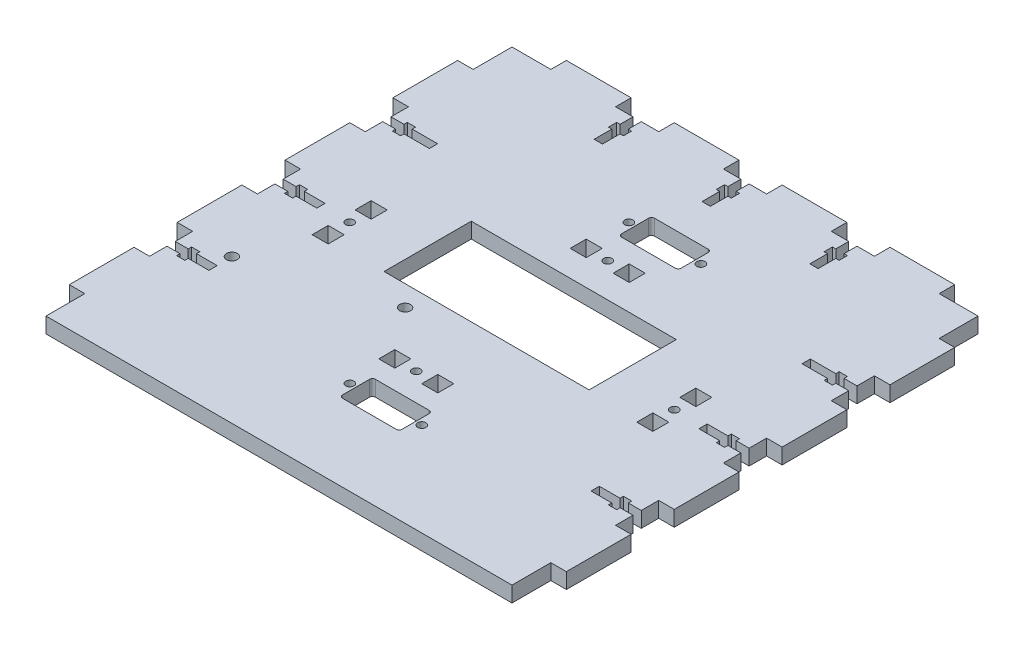
SolidWorks part; units mm, degrees
material "Oak"
ref_plane "Front Plane" through (0, 0, 0) normal (0, 0, 1) x (1, 0, 0)
ref_plane "Top Plane" through (0, 0, 0) normal (0, 1, 0) x (1, 0, 0)
ref_plane "Right Plane" through (0, 0, 0) normal (1, 0, 0) x (0, 0, -1)
sketch "Sketch1" plane through (0, 0, 0) normal (0, 1, 0) x (1, 0, 0)
  line L0 (0, -90) -> (0, 90) construction
  line L2 (90, 43.2667) -> (85, 43.2667)
  line L3 (90, 43.2667) -> (90, 40.0667)
  line L4 (90, 40.0667) -> (85, 40.0667)
  line L5 (72, 43.2667) -> (72, 40.0667)
  line L6 (81.8, 40.0667) -> (72, 40.0667)
  line L7 (81.8, 44.5667) -> (85, 44.5667)
  line L8 (81.8, 44.5667) -> (81.8, 43.2667)
  line L9 (81.8, 38.7667) -> (85, 38.7667)
  line L10 (85, 44.5667) -> (85, 43.2667)
  line L11 (81.8, 40.0667) -> (81.8, 38.7667)
  line L12 (81.8, 43.2667) -> (72, 43.2667)
  line L13 (85, 40.0667) -> (85, 38.7667)
  line L14 (90, 43.2667) -> (90, 50) construction
  line L15 (90, 40.0667) -> (90, 33.3333) construction
  line L16 (-85, 40.0667) -> (-85, 38.7667)
  line L17 (-81.8, 43.2667) -> (-72, 43.2667)
  line L18 (-81.8, 40.0667) -> (-81.8, 38.7667)
  line L19 (-85, 44.5667) -> (-85, 43.2667)
  line L20 (-81.8, 38.7667) -> (-85, 38.7667)
  line L21 (-81.8, 44.5667) -> (-81.8, 43.2667)
  line L22 (-81.8, 44.5667) -> (-85, 44.5667)
  line L23 (-81.8, 40.0667) -> (-72, 40.0667)
  line L24 (-72, 43.2667) -> (-72, 40.0667)
  line L25 (-90, 40.0667) -> (-85, 40.0667)
  line L26 (-90, 43.2667) -> (-90, 40.0667)
  line L27 (-90, 43.2667) -> (-85, 43.2667)
  line L86 (65.8, -11.4) -> (59.6, -11.4)
  line L87 (-65.8, -5.2) -> (-59.6, -5.2)
  line L90 (-65.7, 11.3) -> (-65.7, 5.3) construction
  line L91 (-65.7, 5.3) -> (-59.7, 5.3) construction
  line L92 (-59.7, 5.3) -> (-59.7, 11.3) construction
  line L93 (-59.7, 11.3) -> (-65.7, 11.3) construction
  line L98 (-65.7, 11.3) -> (-65.7, 5.3) construction
  line L99 (-65.7, 5.3) -> (-59.7, 5.3) construction
  line L100 (-59.7, 5.3) -> (-59.7, 11.3) construction
  line L101 (-59.7, 11.3) -> (-65.7, 11.3) construction
  line L102 (-59.6, 11.4) -> (-65.8, 11.4)
  line L103 (-65.8, 11.4) -> (-65.8, 5.2)
  line L104 (-65.8, 5.2) -> (-59.6, 5.2)
  line L105 (-59.6, 5.2) -> (-59.6, 11.4)
  line L114 (65.8, 5.2) -> (59.6, 5.2)
  line L115 (59.6, 5.2) -> (59.6, 11.4)
  line L116 (65.8, 11.4) -> (65.8, 5.2)
  line L117 (59.6, 11.4) -> (65.8, 11.4)
  line L118 (-62.7, 5.2) -> (-62.7, -5.2) construction
  line L119 (-65.8, -5.2) -> (-65.8, -11.4)
  line L120 (-65.8, -11.4) -> (-59.6, -11.4)
  line L121 (-59.6, -5.2) -> (-59.6, -11.4)
  line L122 (59.6, -5.2) -> (59.6, -11.4)
  line L123 (65.8, -5.2) -> (59.6, -5.2)
  line L135 (65.8, -5.2) -> (65.8, -11.4)
  line L142 (-6.1, -59.15) -> (-6.1, -48.65) construction
  line L143 (-5.25, -47.8) -> (15.55, -47.8) construction
  line L144 (15.55, -60) -> (-5.25, -60) construction
  line L145 (16.4, -48.65) -> (16.4, -59.15) construction
  line L146 (-6.1, -59.15) -> (-6.1, -48.65) construction
  line L151 (-5.25, -47.8) -> (15.55, -47.8) construction
  line L152 (15.55, -60) -> (-5.25, -60) construction
  line L153 (16.4, -48.65) -> (16.4, -59.15) construction
  line L154 (-6.35, -59.15) -> (-6.35, -48.65)
  line L160 (-5.25, -47.55) -> (15.55, -47.55)
  line L161 (16.65, -48.65) -> (16.65, -59.15)
  line L162 (15.55, -60.25) -> (-5.25, -60.25)
  line L163 (-3.3, 0) -> (3.3, 0) construction
  line L164 (16.65, 48.65) -> (16.65, 59.15)
  line L165 (15.55, 60.25) -> (-5.25, 60.25)
  line L166 (-6.35, 59.15) -> (-6.35, 48.65)
  line L167 (-5.25, 47.55) -> (15.55, 47.55)
  line L169 (-11.4, 40.0667) -> (-5.2, 40.0667)
  line L170 (-11.4, 40.0667) -> (-11.4, 33.8667)
  line L171 (-11.4, 33.8667) -> (-5.2, 33.8667)
  line L172 (-5.2, 40.0667) -> (-5.2, 33.8667)
  line L173 (11.4, 33.8667) -> (5.2, 33.8667)
  line L174 (5.2, 40.0667) -> (5.2, 33.8667)
  line L175 (11.4, 40.0667) -> (5.2, 40.0667)
  line L176 (11.4, 40.0667) -> (11.4, 33.8667)
  line L177 (11.4, -40.0667) -> (11.4, -33.8667)
  line L178 (11.4, -40.0667) -> (5.2, -40.0667)
  line L179 (5.2, -40.0667) -> (5.2, -33.8667)
  line L180 (11.4, -33.8667) -> (5.2, -33.8667)
  line L181 (-11.4, -33.8667) -> (-5.2, -33.8667)
  line L182 (-5.2, -40.0667) -> (-5.2, -33.8667)
  line L183 (-11.4, -40.0667) -> (-5.2, -40.0667)
  line L184 (-11.4, -40.0667) -> (-11.4, -33.8667)
  line L186 (-39.6, 23.8667) -> (39.6, 23.8667)
  line L187 (-39.6, 23.8667) -> (-39.6, -9.817)
  line L188 (-39.6, -9.817) -> (39.6, -9.817)
  line L189 (39.6, 23.8667) -> (39.6, -9.817)
  circle A0 centre (-62.7, 0) radius 1.6
  circle A1 centre (62.7, 0) radius 1.6
  arc A2 (-6.1, -59.15) -> (-5.25, -60) centre (-5.25, -59.15) ccw construction
  arc A3 (-5.25, -47.8) -> (-6.1, -48.65) centre (-5.25, -48.65) ccw construction
  arc A4 (16.4, -48.65) -> (15.55, -47.8) centre (15.55, -48.65) ccw construction
  arc A11 (15.55, -60) -> (16.4, -59.15) centre (15.55, -59.15) ccw construction
  arc A15 (-6.1, -59.15) -> (-5.25, -60) centre (-5.25, -59.15) ccw construction
  arc A17 (-5.25, -47.8) -> (-6.1, -48.65) centre (-5.25, -48.65) ccw construction
  arc A18 (16.4, -48.65) -> (15.55, -47.8) centre (15.55, -48.65) ccw construction
  arc A19 (15.55, -60) -> (16.4, -59.15) centre (15.55, -59.15) ccw construction
  arc A21 (-5.25, -47.55) -> (-6.35, -48.65) centre (-5.25, -48.65) ccw
  arc A22 (16.65, -48.65) -> (15.55, -47.55) centre (15.55, -48.65) ccw
  arc A23 (15.55, -60.25) -> (16.65, -59.15) centre (15.55, -59.15) ccw
  arc A24 (-6.35, -59.15) -> (-5.25, -60.25) centre (-5.25, -59.15) ccw
  circle A25 centre (-8.75, -53.9) radius 1.6
  circle A26 centre (19.05, -53.9) radius 1.6
  circle A27 centre (19.05, 53.9) radius 1.6
  arc A28 (16.65, 48.65) -> (15.55, 47.55) centre (15.55, 48.65) cw
  arc A29 (15.55, 60.25) -> (16.65, 59.15) centre (15.55, 59.15) cw
  arc A30 (-6.35, 59.15) -> (-5.25, 60.25) centre (-5.25, 59.15) cw
  circle A31 centre (-8.75, 53.9) radius 1.6
  arc A32 (-5.25, 47.55) -> (-6.35, 48.65) centre (-5.25, 48.65) cw
  circle A33 centre (0, 36.9667) radius 1.6
  circle A34 centre (0, -36.9667) radius 1.6
  circle A96 centre (-74.006, -34.2) radius 2 construction
  circle A97 centre (-23.46, -17.817) radius 2 construction
  circle A98 centre (-74.006, -34.2) radius 2 construction
  circle A99 centre (-23.46, -17.817) radius 2 construction
  circle A100 centre (-74.006, -34.2) radius 2.1
  circle A101 centre (-23.46, -17.817) radius 2.1
  point P29 (0, 0)
  point P64 (0, 0)
  point P120 (-5.2, 36.9667)
  line B0 (90, 90) -> (75, 90)
  line B1 (75, 90) -> (75, 96)
  line B2 (75, 96) -> (50, 96)
  line B3 (50, 96) -> (50, 90)
  line B4 (50, 90) -> (43.2667, 90)
  line B5 (43.2667, 90) -> (43.2667, 85)
  line B6 (43.2667, 85) -> (44.5667, 85)
  line B7 (44.5667, 85) -> (44.5667, 81.8)
  line B8 (44.5667, 81.8) -> (43.2667, 81.8)
  line B9 (43.2667, 81.8) -> (43.2667, 75)
  line B10 (43.2667, 75) -> (40.0667, 75)
  line B11 (40.0667, 75) -> (40.0667, 81.8)
  line B12 (40.0667, 81.8) -> (38.7667, 81.8)
  line B13 (38.7667, 81.8) -> (38.7667, 85)
  line B14 (38.7667, 85) -> (40.0667, 85)
  line B15 (40.0667, 85) -> (40.0667, 90)
  line B16 (40.0667, 90) -> (33.3333, 90)
  line B17 (33.3333, 90) -> (33.3333, 96)
  line B18 (33.3333, 96) -> (8.3333, 96)
  line B19 (8.3333, 96) -> (8.3333, 90)
  line B20 (8.3333, 90) -> (1.6, 90)
  line B21 (1.6, 90) -> (1.6, 85)
  line B22 (1.6, 85) -> (2.9, 85)
  line B23 (2.9, 85) -> (2.9, 81.8)
  line B24 (2.9, 81.8) -> (1.6, 81.8)
  line B25 (1.6, 81.8) -> (1.6, 75)
  line B26 (1.6, 75) -> (-1.6, 75)
  line B27 (-1.6, 75) -> (-1.6, 81.8)
  line B28 (-1.6, 81.8) -> (-2.9, 81.8)
  line B29 (-2.9, 81.8) -> (-2.9, 85)
  line B30 (-2.9, 85) -> (-1.6, 85)
  line B31 (-1.6, 85) -> (-1.6, 90)
  line B32 (-1.6, 90) -> (-8.3333, 90)
  line B33 (-8.3333, 90) -> (-8.3333, 96)
  line B34 (-8.3333, 96) -> (-33.3333, 96)
  line B35 (-33.3333, 96) -> (-33.3333, 90)
  line B36 (-33.3333, 90) -> (-40.0667, 90)
  line B37 (-40.0667, 90) -> (-40.0667, 85)
  line B38 (-40.0667, 85) -> (-38.7667, 85)
  line B39 (-38.7667, 85) -> (-38.7667, 81.8)
  line B40 (-38.7667, 81.8) -> (-40.0667, 81.8)
  line B41 (-40.0667, 81.8) -> (-40.0667, 75)
  line B42 (-40.0667, 75) -> (-43.2667, 75)
  line B43 (-43.2667, 75) -> (-43.2667, 81.8)
  line B44 (-43.2667, 81.8) -> (-44.5667, 81.8)
  line B45 (-44.5667, 81.8) -> (-44.5667, 85)
  line B46 (-44.5667, 85) -> (-43.2667, 85)
  line B47 (-43.2667, 85) -> (-43.2667, 90)
  line B48 (-43.2667, 90) -> (-50, 90)
  line B49 (-50, 90) -> (-50, 96)
  line B50 (-50, 96) -> (-75, 96)
  line B51 (-75, 96) -> (-75, 90)
  line B52 (-75, 90) -> (-90, 90)
  line B53 (-90, 90) -> (-90, 75)
  line B54 (-90, 75) -> (-96, 75)
  line B55 (-96, 75) -> (-96, 50)
  line B56 (-96, 50) -> (-90, 50)
  line B57 (-90, 50) -> (-90, 33.3333)
  line B58 (-90, 33.3333) -> (-96, 33.3333)
  line B59 (-96, 33.3333) -> (-96, 8.3333)
  line B60 (-96, 8.3333) -> (-90, 8.3333)
  line B61 (-90, 8.3333) -> (-90, 1.6)
  line B62 (-90, 1.6) -> (-85, 1.6)
  line B63 (-85, 1.6) -> (-85, 2.9)
  line B64 (-85, 2.9) -> (-81.8, 2.9)
  line B65 (-81.8, 2.9) -> (-81.8, 1.6)
  line B66 (-81.8, 1.6) -> (-73.8, 1.6)
  line B67 (-73.8, 1.6) -> (-73.8, -1.6)
  line B68 (-73.8, -1.6) -> (-81.8, -1.6)
  line B69 (-81.8, -1.6) -> (-81.8, -2.9)
  line B70 (-81.8, -2.9) -> (-85, -2.9)
  line B71 (-85, -2.9) -> (-85, -1.6)
  line B72 (-85, -1.6) -> (-90, -1.6)
  line B73 (-90, -1.6) -> (-90, -8.3333)
  line B74 (-90, -8.3333) -> (-96, -8.3333)
  line B75 (-96, -8.3333) -> (-96, -33.3333)
  line B76 (-96, -33.3333) -> (-90, -33.3333)
  line B77 (-90, -33.3333) -> (-90, -40.0667)
  line B78 (-90, -40.0667) -> (-85, -40.0667)
  line B79 (-85, -40.0667) -> (-85, -38.7667)
  line B80 (-85, -38.7667) -> (-81.8, -38.7667)
  line B81 (-81.8, -38.7667) -> (-81.8, -40.0667)
  line B82 (-81.8, -40.0667) -> (-73.8, -40.0667)
  line B83 (-73.8, -40.0667) -> (-73.8, -43.2667)
  line B84 (-73.8, -43.2667) -> (-81.8, -43.2667)
  line B85 (-81.8, -43.2667) -> (-81.8, -44.5667)
  line B86 (-81.8, -44.5667) -> (-85, -44.5667)
  line B87 (-85, -44.5667) -> (-85, -43.2667)
  line B88 (-85, -43.2667) -> (-90, -43.2667)
  line B89 (-90, -43.2667) -> (-90, -50)
  line B90 (-90, -50) -> (-96, -50)
  line B91 (-96, -50) -> (-96, -75)
  line B92 (-96, -75) -> (-90, -75)
  line B93 (-90, -75) -> (-90, -90)
  line B94 (-90, -90) -> (90, -90)
  line B95 (90, -90) -> (90, -75)
  line B96 (90, -75) -> (96, -75)
  line B97 (96, -75) -> (96, -50)
  line B98 (96, -50) -> (90, -50)
  line B99 (90, -50) -> (90, -43.2667)
  line B100 (90, -43.2667) -> (85, -43.2667)
  line B101 (85, -43.2667) -> (85, -44.5667)
  line B102 (85, -44.5667) -> (81.8, -44.5667)
  line B103 (81.8, -44.5667) -> (81.8, -43.2667)
  line B104 (81.8, -43.2667) -> (73.8, -43.2667)
  line B105 (73.8, -43.2667) -> (73.8, -40.0667)
  line B106 (73.8, -40.0667) -> (81.8, -40.0667)
  line B107 (81.8, -40.0667) -> (81.8, -38.7667)
  line B108 (81.8, -38.7667) -> (85, -38.7667)
  line B109 (85, -38.7667) -> (85, -40.0667)
  line B110 (85, -40.0667) -> (90, -40.0667)
  line B111 (90, -40.0667) -> (90, -33.3333)
  line B112 (90, -33.3333) -> (96, -33.3333)
  line B113 (96, -33.3333) -> (96, -8.3333)
  line B114 (96, -8.3333) -> (90, -8.3333)
  line B115 (90, -8.3333) -> (90, -1.6)
  line B116 (90, -1.6) -> (85, -1.6)
  line B117 (85, -1.6) -> (85, -2.9)
  line B118 (85, -2.9) -> (81.8, -2.9)
  line B119 (81.8, -2.9) -> (81.8, -1.6)
  line B120 (81.8, -1.6) -> (73.8, -1.6)
  line B121 (73.8, -1.6) -> (73.8, 1.6)
  line B122 (73.8, 1.6) -> (81.8, 1.6)
  line B123 (81.8, 1.6) -> (81.8, 2.9)
  line B124 (81.8, 2.9) -> (85, 2.9)
  line B125 (85, 2.9) -> (85, 1.6)
  line B126 (85, 1.6) -> (90, 1.6)
  line B127 (90, 1.6) -> (90, 8.3333)
  line B128 (90, 8.3333) -> (96, 8.3333)
  line B129 (96, 8.3333) -> (96, 33.3333)
  line B130 (96, 33.3333) -> (90, 33.3333)
  line B131 (90, 33.3333) -> (90, 50)
  line B132 (90, 50) -> (96, 50)
  line B133 (96, 50) -> (96, 75)
  line B134 (96, 75) -> (90, 75)
  line B135 (90, 75) -> (90, 90)
  dimension "D14" = 3.2
  dimension "D16" = 3.2
  dimension "D17" = 3.2
  dimension "D18" = 20
  dimension "D19" = 10
  dimension "D10" = 3.2
  dimension "D1" = 3.2
  dimension "D2" = 5.8
  dimension "D3" = 3.2
  dimension "D4" = 18
  dimension "D5" = 5
  dimension "D6" = 10.4
  dimension "D7" = 10.4
  dimension "D8" = 6.2
  dimension "D11" = 0.1
  dimension "D12" = 30.2
  dimension "D9" = 5.2
  dimension "D20" = 6.2
  dimension "D21" = 8
  dimension "D13" = 20
  dimension "D15" = 0.25
sketch_block_instance "MainBody-1"
sketch_block "MainBody"
extrude "Boss-Extrude1" add sketch "Sketch1" along normal blind 6 contours B134 B135 B0 B1 B2 B3 B4 B5 B6 B7 B8 B9 B10 B11 B12 B13 B14 B15 B16 B17 B18 B19 B20 B21 B22 B23 B24 B25 B26 B27 B28 B29 B30 B31 B32 B33 B34 B35 B36 B37 B38 B39 B40 B41 B42 B43 B44 B45 B46 B47 B48 region at (87.5, 0, -45.9399)
